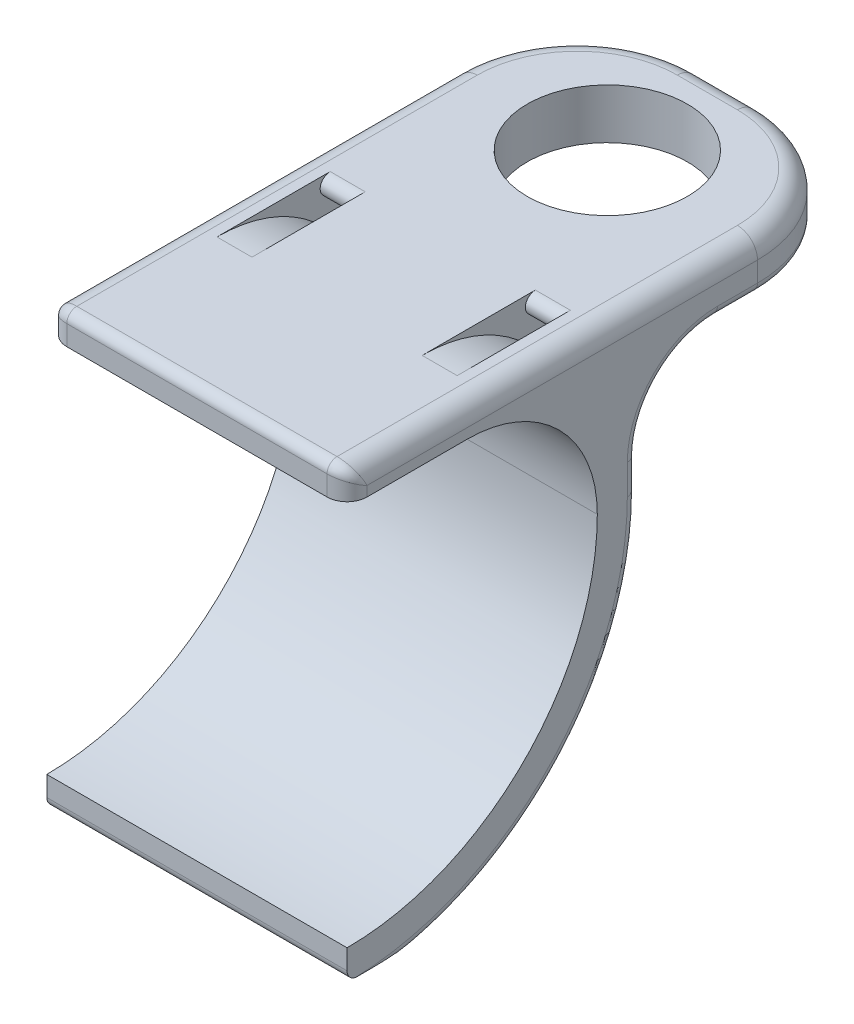
SolidWorks part; units mm, degrees
ref_plane "Front Plane" through (0, 0, 0) normal (0, 0, 1) x (1, 0, 0)
ref_plane "Top Plane" through (0, 0, 0) normal (0, 1, 0) x (1, 0, 0)
ref_plane "Right Plane" through (0, 0, 0) normal (1, 0, 0) x (0, 0, -1)
sketch "Sketch1" plane through (0, 0, 0) normal (1, 0, 0) x (0, 0, -1)
  line L0 (0, 13) -> (-12, 13)
  line L1 (-12, 13) -> (-12, 16)
  line L2 (-12, 16) -> (41, 16)
  line L3 (41, 16) -> (41, 11)
  line L4 (-12, -25) -> (-12, -28)
  line L5 (-12, -28) -> (-4.4502, -28)
  line L6 (13, 37.1451) -> (13, -18.3215) construction
  line L7 (41, 11) -> (17, 11)
  line L8 (17, 11) -> (17, 0)
  arc A0 (0, 13) -> (13, 0) centre (0, 0) cw
  arc A1 (13, 0) -> (-12, -25) centre (-12, 0) cw
  arc A2 (17, 0) -> (-4.4502, -28) centre (-12, 0) cw
  point P8 (0, 0)
  point P15 (16, -2.3599)
  point P16 (-3.2421, -27)
  point P17 (16, 0)
  point P18 (0, -27)
  point P20 (-1.77, -27)
  point P21 (0, 0)
  point P22 (40, 11.798)
  dimension "D6" = 4
  dimension "D7" = 5
  dimension "D1" = 3
  dimension "D2" = 25
  dimension "D3" = 3
  dimension "D4" = 38
  dimension "D5" = 24
extrude "Boss-Extrude1" add sketch "Sketch1" along normal blind 30
sketch "Sketch2" plane through (30, 0, 0) normal (1, 0, 0) x (0, 0, -1)
  line L0 (41, 16) -> (-12, 16) construction
  line L1 (2, 16) -> (10, 16)
  line L2 (17, 0) -> (17, 11) construction
  line L3 (17, 1) -> (17, 9)
  arc A0 (2, 16) -> (17, 1) centre (2, 1) cw
  arc A2 (10, 16) -> (17, 9) centre (2, 1) cw
  point P5 (0, 0)
  dimension "D1" = 15
  dimension "D2" = 2
extrude "Cut-Extrude1" cut sketch "Sketch2" against normal blind 3.5 from offset 3 offset against normal yes
extrude "Cut-Extrude2" cut sketch "Sketch2<2>" against normal blind 3.5 from offset 23.5 offset against normal yes
sketch "Sketch2<2>" plane through (30, 0, 0) normal (1, 0, 0) x (0, 0, -1) same geometry as "Sketch2"
fillet "Fillet1" radius 1 2 edges at (25.25, 16, -10) (4.75, 16, -10)
fillet "Fillet2" radius 8 1 edges at (15, 11, -17)
fillet "Fillet3" radius 1 2 edges at (4.75, 6.8219, -17.972) (25.25, 6.8219, -17.972)
fillet "Fillet4" radius 12 2 edges at (0, 13.5, -41) (30, 13.5, -41)
sketch "Sketch3" plane through (0, 16, 0) normal (0, 1, 0) x (1, 0, 0)
  line L0 (15, 41) -> (15, 29) construction
  line L1 (18, 41) -> (12, 41) construction
  circle A0 centre (15, 29) radius 8
  dimension "D1" = 16
  dimension "D2" = 12
extrude "Cut-Extrude3" cut sketch "Sketch3" against normal up to next
sketch "Sketch4" plane through (0, 11, 0) normal (0, -1, 0) x (1, 0, 0)
  circle A0 centre (15, -29) radius 11
  dimension "D1" = 22
extrude "Cut-Extrude4" cut sketch "Sketch4" along normal up to next
fillet "Fillet5" radius 3 1 edges at (14.026, 6.9501, -18.0432)
fillet "Fillet6" radius 1 11 edges at (30, -17.636, -11.0211) (30, 1.5, -17) (30, 8.6569, -19.3431) (30, 11, -27) (26.4853, 11, -37.4853) (0, -17.636, -11.0211) (0, 1.5, -17) (0, 8.6569, -19.3431) (0, 11, -27) (3.5147, 11, -37.4853) (15, 11, -41)
fillet "Fillet8" radius 1 2 edges at (15, 16, 12) (15, -28, 12)
fillet "Fillet9" radius 2 9 edges at (30, 14, 12) (30, 15.7071, 11.7071) (30, 16, -9) (26.4853, 16, -37.4853) (0, 14, 12) (0, 15.7071, 11.7071) (0, 16, -9) (3.5147, 16, -37.4853) (15, 16, -41)
